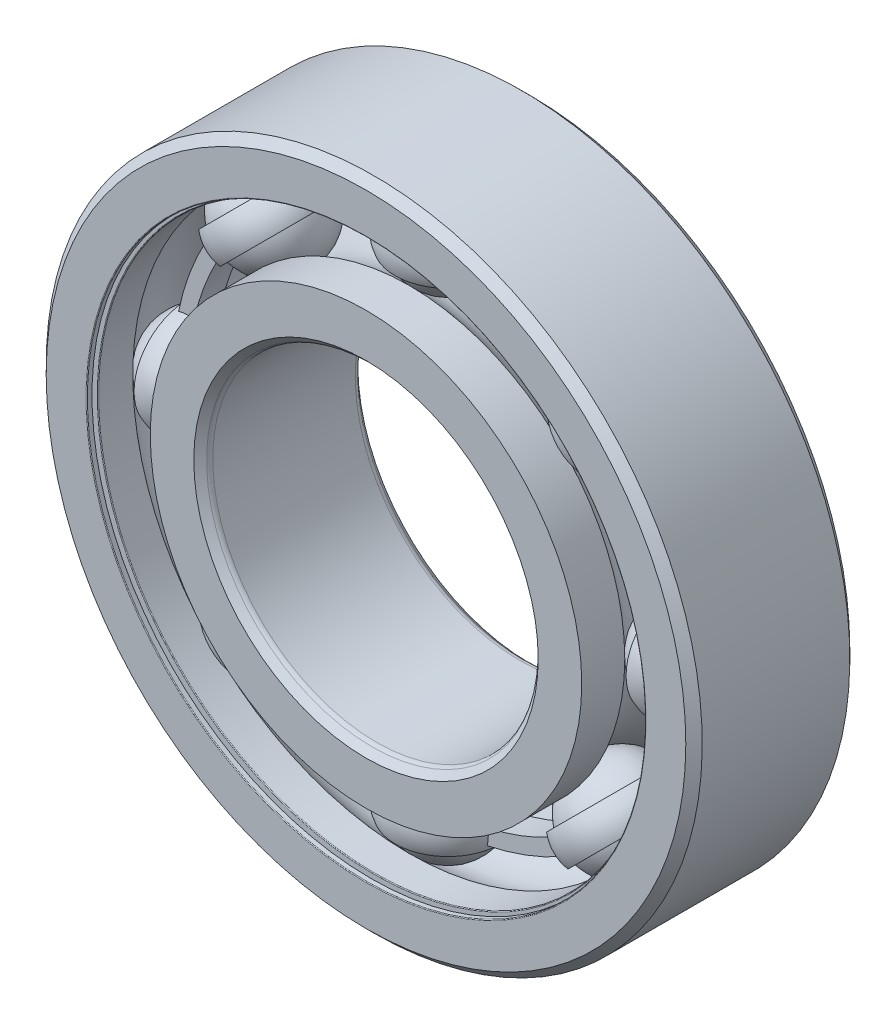
SolidWorks part; units mm, degrees
ref_plane "Front Plane" through (0, 0, 0) normal (0, 0, 1) x (1, 0, 0)
ref_plane "Top Plane" through (0, 0, 0) normal (0, 1, 0) x (1, 0, 0)
ref_plane "Right Plane" through (0, 0, 0) normal (1, 0, 0) x (0, 0, -1)
sketch "Sketch1" plane through (0, 0, 0) normal (0, 0, 1) x (1, 0, 0)
  line L0 (-12, 0) -> (12, 0) construction
  line L1 (-6, 0) -> (6, 0) construction
  circle A0 centre (0, 0) radius 6 construction
  circle A1 centre (0, 0) radius 12 construction
  point P3 (0, 0)
  point P6 (0, 0)
  point P7 (0, -6)
  point P11 (0, -12)
  point P12 (0, 6)
  point P13 (0, 12)
  dimension "OD" = 24
  dimension "ID" = 12
sketch "Sketch2" plane through (0, 0, 0) normal (1, 0, 0) x (0, 0, -1)
  line L0 (-3, 12) -> (3, 12) construction
  line L1 (0, 12) -> (0, -12) construction
  line L2 (2.7, 12) -> (-2.7, 12)
  line L3 (-2.7, 12) -> (-3, 11.7)
  line L4 (-3, 11.7) -> (-3, 10.1077)
  line L5 (-3, 10.1077) -> (-1.425, 10.1077)
  line L6 (3, 10.1077) -> (1.425, 10.1077)
  line L7 (3, 11.7) -> (3, 10.1077)
  line L8 (2.7, 12) -> (3, 11.7)
  line L9 (0, 12) -> (0, 9) construction
  line L10 (0, 9) -> (0, 6) construction
  line L11 (0, 12) -> (0, -12) construction
  line L12 (-3, 0) -> (3, 0) construction
  line L13 (3, 6) -> (-3, 6) construction
  line L14 (0, 10.8049) -> (0, 7.1951) construction
  line L15 (-3, -6) -> (3, -6) construction
  line L16 (-3, -6) -> (-3, 6) construction
  line L17 (3, 12) -> (3, -12) construction
  arc A0 (-1.425, 10.1077) -> (1.425, 10.1077) centre (0, 9) cw
  circle A1 centre (0, 9) radius 1.8049 construction
  point P14 (0, 6)
  point P17 (0, 0)
  point P21 (0, 12)
  point P29 (0, 6)
  point P30 (0, -6)
  point P35 (0, 10.8049)
  dimension "Approx. Ball Dia." = 3.6098
  dimension "Width" = 6
  dimension "D1" = 45
  dimension "D2" = 0.3
  dimension "D3" = 2.85
  dimension "D4" = 1.1077
  dimension "For Shaft Diameter" = 12
  dimension "For Housing ID" = 24
sketch "Sketch3" plane through (0, 0, 0) normal (1, 0, 0) x (0, 0, -1)
  line L0 (2.7, 12) -> (3, 11.7) construction
  line L1 (3, 11.7) -> (3, 10.1077) construction
  line L2 (3, 10.1077) -> (1.425, 10.1077) construction
  line L3 (-3, 10.1077) -> (-1.425, 10.1077) construction
  line L4 (-3, 11.7) -> (-3, 10.1077) construction
  line L5 (-2.7, 12) -> (-3, 11.7) construction
  line L6 (2.7, 12) -> (-2.7, 12) construction
  line L7 (2.7, 12) -> (3, 11.7)
  line L8 (3, 11.7) -> (3, 10.1077)
  line L9 (3, 10.1077) -> (1.425, 10.1077)
  line L10 (-3, 10.1077) -> (-1.425, 10.1077)
  line L11 (-3, 11.7) -> (-3, 10.1077)
  line L12 (-2.7, 12) -> (-3, 11.7)
  line L13 (2.7, 12) -> (-2.7, 12)
  arc A0 (1.425, 10.1077) -> (-1.425, 10.1077) centre (0, 9) ccw construction
  arc A1 (1.425, 10.1077) -> (-1.425, 10.1077) centre (0, 9) ccw
revolve "Revolve1" add sketch "Sketch3" angle 360 about L12
sketch "Sketch8" plane through (0, 0, 0) normal (1, 0, 0) x (0, 0, -1)
  line L0 (-3, 10.1077) -> (-1.425, 10.1077) construction
  line L1 (-2.808, 10.1077) -> (-2.7, 10.1077)
  line L2 (-2.808, 10.1077) -> (-2.808, 10.7385) construction
  line L3 (-2.808, 10.7385) -> (-2.7, 10.7385)
  line L4 (-2.7, 10.1077) -> (-2.7, 10.7385)
  line L5 (3, 10.1077) -> (1.425, 10.1077) construction
  line L6 (2.7, 10.1077) -> (2.808, 10.1077)
  line L7 (2.7, 10.1077) -> (2.7, 10.7385)
  line L8 (2.7, 10.7385) -> (2.808, 10.7385)
  line L9 (2.808, 10.1077) -> (2.808, 10.7385) construction
  line L10 (-2.7, 10.7385) -> (2.7, 10.7385) construction
  line L11 (0, 12) -> (0, -12) construction
  line L12 (-2.808, 10.7385) -> (-2.808, 11.3692) construction
  line L13 (-2.808, 11.3692) -> (-2.808, 12) construction
  line L14 (-3, 12) -> (3, 12) construction
  line L15 (-2.808, 10.1077) -> (-3, 10.1077)
  line L16 (-3, 10.1077) -> (-3, 10.2157)
  line L17 (-3, 11.7) -> (-3, 10.1077) construction
  line L18 (-3, 10.2157) -> (-2.808, 10.2157)
  line L19 (-2.808, 10.2157) -> (-2.808, 10.7385)
  line L20 (2.808, 10.1077) -> (3, 10.1077)
  line L21 (3, 10.1077) -> (3, 10.2157)
  line L22 (3, 11.7) -> (3, 10.1077) construction
  line L23 (3, 10.2157) -> (2.808, 10.2157)
  line L24 (2.808, 10.2157) -> (2.808, 10.7385)
  point P12 (0, 10.7385)
  dimension "D1" = 5.4
  dimension "D2" = 0.108
revolve "Cut-Revolve1" cut sketch "Sketch8" angle 360 about L12
sketch "Sketch4" plane through (0, 0, 0) normal (1, 0, 0) x (0, 0, -1)
  line L0 (0, 12) -> (0, -12) construction
  line L1 (0, 12) -> (0, -12) construction
  line L2 (-2.7, 6) -> (-3, 6.3)
  line L3 (-3, 6.3) -> (-3, 7.8923)
  line L5 (-3, 7.8923) -> (-1.425, 7.8923)
  line L6 (-2.7, 6) -> (2.7, 6)
  line L8 (2.7, 6) -> (3, 6.3)
  line L10 (3, 6.3) -> (3, 7.8923)
  line L11 (3, 7.8923) -> (1.425, 7.8923)
  line L12 (-3, 11.7) -> (-3, 10.1077) construction
  line L13 (2.7, 12) -> (3, 11.7) construction
  line L15 (3, -11.7) -> (3, 11.7) construction
  line L16 (2.7, 12) -> (2.7, -12) construction
  arc A1 (1.425, 7.8923) -> (-1.425, 7.8923) centre (0, 9) cw
  circle A2 centre (0, 9) radius 1.8049 construction
  point P1 (0, 6)
revolve "Revolve2" add sketch "Sketch4" angle 360 about L12
sketch "Sketch5" plane through (0, 0, 0) normal (1, 0, 0) x (0, 0, -1)
  line L0 (-1.8049, 9) -> (1.8049, 9)
  arc A2 (-1.8049, 9) -> (1.8049, 9) centre (0, 9) cw
  arc A3 (1.425, 10.1077) -> (-1.425, 10.1077) centre (0, 9) ccw construction
revolve "Revolve3" add sketch "Sketch5" angle 360 about L0
sketch "Sketch6" plane through (0, 0, 0) normal (1, 0, 0) x (0, 0, -1)
  line L0 (-1.425, 10.1077) -> (-1.425, 9.5538) construction
  line L1 (-1.425, 9.5538) -> (-1.425, 9) construction
  line L2 (-1.425, 9) -> (-1.425, 8.4462) construction
  line L3 (-1.425, 8.4462) -> (-1.425, 7.8923) construction
  line L4 (-3, 9.5538) -> (-2.7863, 9.5538) construction
  line L5 (-1.425, 9.5538) -> (-1.425, 8.4462) construction
  line L7 (-2.7863, 9.5538) -> (-2.5726, 9.5538) construction
  line L8 (-2.5726, 9.5538) -> (-2.3589, 9.5538) construction
  line L10 (0, 12) -> (0, -12) construction
  line L11 (0, 12) -> (0, -12) construction
  line L12 (-3, 10.1077) -> (-3, 9.5538) construction
  line L13 (-1.9315, 9.5538) -> (-1.7178, 9.5538) construction
  line L14 (-3, 11.7) -> (-3, -11.7) construction
  line L15 (-3, 9.5538) -> (-3, 9) construction
  line L16 (-3, 9) -> (-3, 8.4462) construction
  line L17 (-3, 8.4462) -> (-3, 7.8923) construction
  line L18 (-2.3589, 9.5538) -> (-2.1452, 9.5538) construction
  line L19 (-2.1452, 9.5538) -> (-1.9315, 9.5538) construction
  line L20 (-1.7178, 9.5538) -> (-1.9315, 9.5538)
  line L21 (-3, 8.4462) -> (-2.7863, 8.4462) construction
  line L22 (-2.7863, 8.4462) -> (-2.5726, 8.4462) construction
  line L23 (-2.5726, 8.4462) -> (-2.3589, 8.4462) construction
  line L24 (-2.3589, 8.4462) -> (-2.1452, 8.4462) construction
  line L25 (-2.1452, 8.4462) -> (-1.9315, 8.4462) construction
  line L26 (-1.9315, 8.4462) -> (-1.7178, 8.4462) construction
  line L27 (-1.7178, 8.4462) -> (-1.9315, 8.4462)
  line L28 (-2.1452, 9.5538) -> (-2.1452, 8.4462) construction
  line L30 (-2.0384, 9.5538) -> (-2.0384, 8.4462) construction
  circle A0 centre (0, 9) radius 1.8049 construction
  arc A2 (-1.9315, 8.4462) -> (-1.9315, 9.5538) centre (-0.5495, 9) cw
  arc A3 (-1.7178, 9.5538) -> (-1.7178, 8.4462) centre (0, 9) ccw
revolve "Revolve4" add sketch "Sketch6" angle 360 about L11
sketch "Sketch7" plane through (0, 0, 0) normal (0, 0, 1) x (1, 0, 0)
  line L0 (-1.8049, 9) -> (1.8049, 9) construction
  line L1 (0, 7.1951) -> (0, 10.8049) construction
  line L2 (0, 0) -> (3.4442, 8.3149) construction
  line L8 (0, 12) -> (0, -12) construction
  line L9 (6.364, 6.364) -> (6.7556, 6.7556)
  line L10 (0, 12) -> (0, -12) construction
  line L11 (0, 9.5538) -> (0, 9)
  arc A1 (6.364, 6.364) -> (0, 9) centre (0, 0) ccw
  arc A2 (6.7556, 6.7556) -> (0, 9.5538) centre (0, 0) ccw
  dimension "D1" = 45
  dimension "D2" = 3.6098
extrude "Boss-Extrude1" add sketch "Sketch7" along normal mid plane 1
pattern_circular "CirPattern1" count 8 over 360 about axis through (0, 0, 3) along (0, 0, -1) of bodies 104 134
pattern_circular "CirPattern2" count 8 over 360 about axis through (0, 0, 3) along (0, 0, -1) of "Revolve4", "Boss-Extrude1" reverse direction yes
fillet "Fillet1" radius 0.027 4 edges at (0, -10.1077, -2.7) (0, -10.2157, -3) (0, -10.1077, 2.7) (0, -10.2157, 3)
fillet "Fillet2" radius 0.225 2 edges at (0, -6, -2.7) (0, -6, 2.7)
ref_plane "Plane1" through (3.4442, 8.3149, 0) normal (0.3827, 0.9239, 0) x (0.9239, -0.3827, 0)
sketch "Sketch9" plane through (3.4442, 8.3149, 0) normal (0.3827, 0.9239, 0) x (0.9239, -0.3827, 0)
  line L0 (-1.7767, -0.5) -> (-1.7767, -1.5)
  line L1 (-1.7767, -1.5) -> (-0.7706, -1.5)
  line L2 (-0.7706, -1.5) -> (0, -0.8534)
  line L3 (0, -0.8534) -> (0.7706, -1.5)
  line L4 (0.7706, -1.5) -> (1.7767, -1.5)
  line L5 (1.7767, -1.5) -> (1.7767, -0.5)
  line L6 (1.7767, -0.5) -> (-1.7767, -0.5)
  line L7 (0, -0.5) -> (0, 0) construction
  line L8 (-1.7767, -0.5) -> (-1.7767, 0) construction
  dimension "D1" = 1
  dimension "D2" = 0.5
  dimension "D3" = 40
extrude "Boss-Extrude2" [suppressed] add sketch "Sketch9" along normal blind 1.5793 draft 15 and the other way blind 1.5793 draft 10 separate body draft outward yes other way draft outward yes
fillet "Fillet3" [suppressed] radius 0.3
mirror "Mirror1" [suppressed] about plane through (0, 0, 0) normal (0, 0, 1) of bodies 149
pattern_circular "CirPattern3" [suppressed] count 8 over 360 about axis through (0, 0, 3) along (0, 0, -1) of bodies 158 149
equation "\"D2@Sketch2\" = \"Width@Sketch2\" * .05"
equation "\"D3@Sketch2\"=\"Width@Sketch2\" * .475"
equation "\"D4@Sketch2\" =  (  (  ( \"OD@Sketch1\" - \"Width@Sketch2\" )  / 2 )  / 3.25 )  / 2.5"
equation "\"D1@Boss-Extrude1\" = \"Width@Sketch2\" / 6"
equation "\"D1@Sketch8\"=\"Width@Sketch2\"*.9"
equation "\"D2@Sketch8\"=\"D1@Sketch8\"*.02"
equation "\"D1@Fillet1\" = \"D2@Sketch8\" * .25"
equation "\"D1@Fillet2\" = \"D2@Sketch2\" * .75"
equation "\"Approx No of Balls@CirPattern1\" = ( pi * \"OD@Sketch1\" ) * .4 / \"Approx. Ball Dia.@Sketch2\""
equation "\"D1@Sketch7\" = 360 / \"Approx No of Balls@CirPattern1\""
equation "\"D1@CirPattern2\" = \"Approx No of Balls@CirPattern1\""
equation "\"D2@Sketch7\"=\"Approx. Ball Dia.@Sketch2\""
equation "\"D2@Sketch9\" = \"D1@Boss-Extrude1\" * .5"
equation "\"D1@Sketch9\"=\"D2@Sketch9\"*2"
equation "\"D1@Boss-Extrude2\"=\"Approx. Ball Dia.@Sketch2\"*.4375"
equation "\"D2@Boss-Extrude2\"=\"D1@Boss-Extrude2\""
equation "\"D1@CirPattern3\" = \"Approx No of Balls@CirPattern1\""
equation "\"D1@Fillet3\"=\"D1@Sketch9\" * .3"
